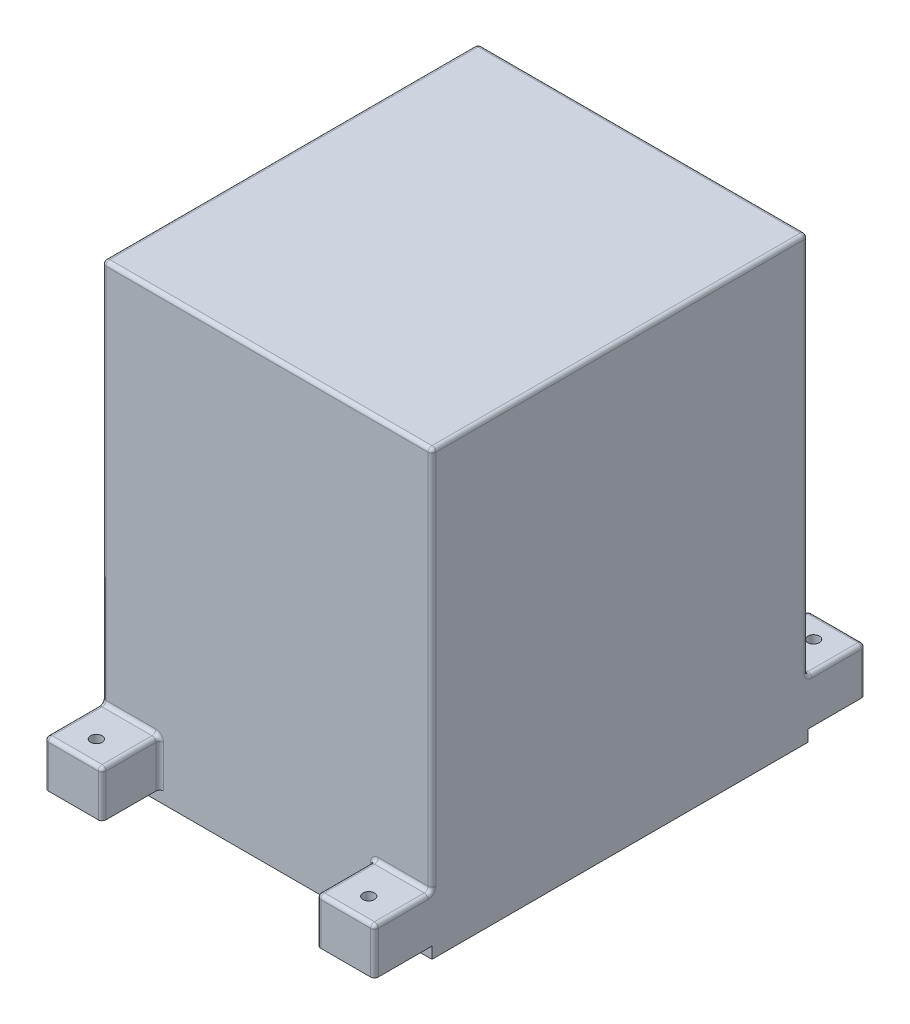
SolidWorks part; units mm, degrees
ref_plane "Plano frontal" through (0, 0, 0) normal (0, 0, 1) x (1, 0, 0)
ref_plane "Plano superior" through (0, 0, 0) normal (0, 1, 0) x (1, 0, 0)
ref_plane "Plano direito" through (0, 0, 0) normal (1, 0, 0) x (0, 0, -1)
sketch "Esboço1" plane through (0, 0, 0) normal (0, 1, 0) x (1, 0, 0)
  line L1 (-354, 441) -> (-440, 441)
  line L2 (-354, 441) -> (-354, 539)
  line L3 (-354, 539) -> (-440, 539)
  line L4 (-440, 441) -> (-440, 539)
  line L9 (-437, 536) -> (-357, 536)
  line L10 (-437, 536) -> (-437, 444)
  line L11 (-437, 444) -> (-357, 444)
  line L12 (-357, 536) -> (-357, 444)
extrude "Ressalto-extrusão1" add sketch "Esboço1" along normal blind 110
sketch "Esboço2" plane through (0, 110, 0) normal (0, 1, 0) x (1, 0, 0)
  line L1 (-440, 441) -> (-354, 441)
  line L2 (-440, 441) -> (-440, 539)
  line L3 (-440, 539) -> (-354, 539)
  line L4 (-354, 441) -> (-354, 539)
extrude "Ressalto-extrusão2" add sketch "Esboço2" along normal blind 5
sketch "Esboço3" plane through (0, 110, 0) normal (0, -1, 0) x (1, 0, 0)
  line L1 (-437, -444) -> (-430, -444)
  line L2 (-437, -444) -> (-437, -454)
  line L3 (-437, -454) -> (-430, -454)
  line L4 (-430, -444) -> (-430, -454)
  line L5 (-357, -444) -> (-364, -444)
  line L6 (-357, -444) -> (-357, -454)
  line L7 (-357, -454) -> (-364, -454)
  line L8 (-364, -444) -> (-364, -454)
  line L10 (-357, -536) -> (-364, -536)
  line L11 (-357, -536) -> (-357, -526)
  line L12 (-357, -526) -> (-364, -526)
  line L14 (-364, -536) -> (-364, -526)
  line L15 (-437, -536) -> (-430, -536)
  line L16 (-437, -536) -> (-437, -526)
  line L17 (-437, -526) -> (-430, -526)
  line L18 (-430, -536) -> (-430, -526)
extrude "Ressalto-extrusão3" add sketch "Esboço3" along normal blind 40
sketch "Esboço4" plane through (-440, 0, 0) normal (-1, 0, 0) x (0, 0, 1)
  circle A0 centre (-450.5, 55.5) radius 3.4996
extrude "Corte-extrusão1" cut sketch "Esboço4" against normal blind 40
fillet "Filete1" radius 1 1 edges at (-437, 55.5, -453.9996)
fillet "Filete2" radius 2 7 edges at (-433.5, 110, -454) (-437, 110, -490) (-397, 110, -444) (-437, 90, -454) (-430, 90, -444) (-430, 90, -454) (-430, 110, -449)
fillet "Filete3" radius 2 19 edges at (-432.5, 110, -526) (-436.4142, 109.4142, -526) (-364, 109.4142, -444.5858) (-437, 89, -526) (-430, 90, -526) (-430, 90, -536) (-430, 110, -531) (-397, 110, -536) (-364, 90, -536) (-357, 90, -526) (-364, 90, -526) (-360.5, 110, -526) (-364, 110, -531) (-357, 110, -490) (-360.5, 110, -454) (-357, 90, -454) (-364, 89, -444) (-364, 90, -454) (-364, 110, -450)
sketch "Esboço5" plane through (0, 0, 0) normal (0, -1, 0) x (1, 0, 0)
  line L1 (-440, -441) -> (-425, -441)
  line L2 (-440, -441) -> (-440, -426)
  line L3 (-440, -426) -> (-425, -426)
  line L4 (-425, -441) -> (-425, -426)
  line L5 (-354, -441) -> (-369, -441)
  line L6 (-354, -441) -> (-354, -426)
  line L7 (-354, -426) -> (-369, -426)
  line L8 (-369, -441) -> (-369, -426)
  line L9 (-440, -539) -> (-425, -539)
  line L10 (-440, -539) -> (-440, -554)
  line L11 (-440, -554) -> (-425, -554)
  line L12 (-425, -539) -> (-425, -554)
  line L13 (-354, -539) -> (-369, -539)
  line L14 (-354, -539) -> (-354, -554)
  line L15 (-354, -554) -> (-369, -554)
  line L16 (-369, -539) -> (-369, -554)
  dimension "D1" = 15
  dimension "D2" = 15
  dimension "D3" = 15
  dimension "D4" = 15
  dimension "D5" = 15
  dimension "D6" = 15
  dimension "D7" = 15
  dimension "D8" = 15
extrude "Ressalto-extrusão4" add sketch "Esboço5" against normal blind 15
sketch "Esboço7" plane through (0, 0, -554) normal (0, 0, -1) x (-1, 0, 0)
  line L0 (425, 15) -> (425, 0) construction
  line L1 (440, 0) -> (425, 0)
  line L2 (440, 0) -> (440, 3)
  line L3 (440, 3) -> (425, 3)
  line L4 (425, 0) -> (425, 3)
  line L5 (354, 15) -> (354, 0) construction
  line L6 (369, 0) -> (354, 0)
  line L7 (369, 0) -> (369, 3)
  line L8 (369, 3) -> (354, 3)
  line L9 (354, 0) -> (354, 3)
  dimension "D1" = 3
extrude "Corte-extrusão2" cut sketch "Esboço7" against normal blind 15
sketch "Esboço8" plane through (0, 0, -426) normal (0, 0, 1) x (1, 0, 0)
  line L0 (-425, 15) -> (-425, 0) construction
  line L1 (-440, 0) -> (-425, 0)
  line L2 (-440, 0) -> (-440, 3)
  line L3 (-440, 3) -> (-425, 3)
  line L4 (-425, 0) -> (-425, 3)
  line L6 (-369, 0) -> (-354, 0)
  line L7 (-369, 0) -> (-369, 3)
  line L8 (-369, 3) -> (-354, 3)
  line L9 (-354, 0) -> (-354, 3)
  dimension "D1" = 3
extrude "Corte-extrusão3" cut sketch "Esboço8" against normal blind 15
fillet "Filete4" radius 1 6 edges at (-425, 15, -433.5) (-432.5, 15, -426)
fillet "Filete5" radius 1 4 edges at (-425.2929, 14.7071, -426.2929) (-439.7071, 14.7071, -426.2929) (-425, 8.5, -426) (-440, 8.5, -426)
fillet "Filete6" radius 1 11 edges at (-354, 15, -433.5) (-361.5, 15, -441) (-440, 115, -490.5) (-439.7071, 115, -441.2929) (-396.5, 115, -441) (-354, 65, -441) (-361.5, 15, -426) (-369, 15, -433.5) (-354, 9, -426) (-369, 9, -426) (-369, 9, -441)
fillet "Filete7" radius 1 20 edges at (-439.7071, 114.7071, -539) (-354.2929, 114.7071, -441.2929) (-354, 9, -554) (-354, 15, -546.5) (-369, 9, -554) (-369, 15, -546.5) (-432.5, 15, -554) (-361.5, 15, -554) (-361.5, 15, -539) (-369, 9, -539) (-440, 9, -554) (-425, 9, -554) (-425, 15, -546.5) (-354, 65, -539) (-396.5, 115, -539) (-354, 115, -490.5)
sketch "Esboço9" plane through (0, 3, 0) normal (0, -1, 0) x (1, 0, 0)
  circle A0 centre (-432.5, -432) radius 1.5
  circle A1 centre (-361.5, -432) radius 1.5
  circle A2 centre (-361.5, -548) radius 1.5
  circle A3 centre (-432.5, -548) radius 1.5
  dimension "D1" = 3
  dimension "D3" = 3
  dimension "D4" = 3
  dimension "D6" = 3
extrude "Corte-extrusão4" cut sketch "Esboço9" against normal blind 15
fillet "Filete8" radius 0.5 4 edges at (-360, 3, -432) (-431, 3, -432) (-431, 3, -548) (-360, 3, -548)
